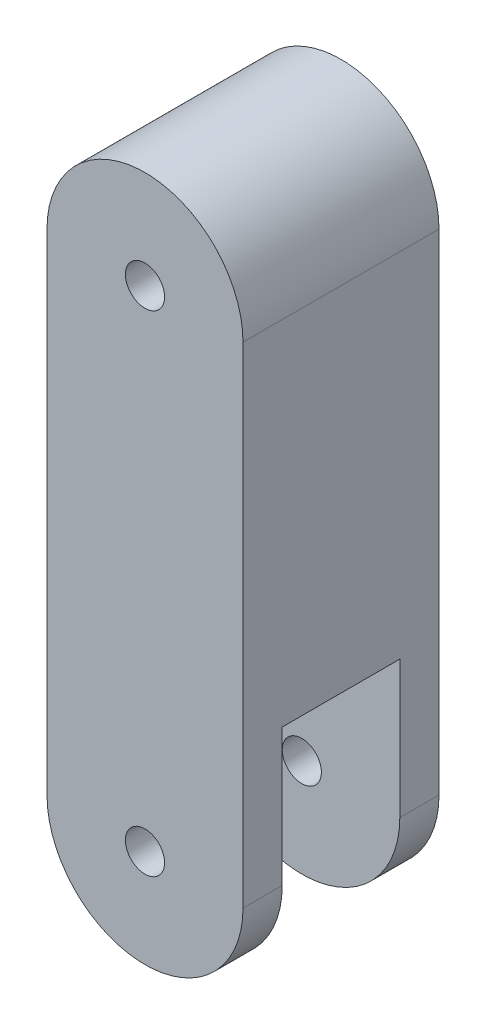
SolidWorks part; units mm, degrees
ref_plane "Alzado" through (0, 0, 0) normal (0, 0, 1) x (1, 0, 0)
ref_plane "Planta" through (0, 0, 0) normal (0, 1, 0) x (1, 0, 0)
ref_plane "Vista lateral" through (0, 0, 0) normal (1, 0, 0) x (0, 0, -1)
sketch "Croquis1" plane through (0, 0, 0) normal (0, 0, 1) x (1, 0, 0)
  line L0 (-2.5, 0) -> (-2.5, -12.5)
  line L3 (2.5, 0) -> (2.5, -12.5)
  line L7 (-2.5, -12.5) -> (-2.5, -10)
  line L8 (-2.5, -10) -> (2.5, -15) construction
  circle A0 centre (0, 0) radius 0.5
  arc A1 (2.5, 0) -> (-2.5, 0) centre (0, 0) ccw
  circle A2 centre (0, -12.5) radius 0.5
  arc A3 (-2.5, -12.5) -> (2.5, -12.5) centre (0, -12.5) ccw
  dimension "D1" = 1
  dimension "D2" = 5
  dimension "D8" = 1
  dimension "D6" = 15
extrude "Saliente-Extruir2" add sketch "Croquis1" along normal blind 5 contours L0 L8 A2 A3 L3 A1 A0 | L8 L0 A3 A2 region at (0.1253, -5.2662, 0) region at (-0.8749, -13.1169, 0)
sketch "Croquis3" plane through (2.5, 0, 0) normal (1, 0, 0) x (0, 0, -1)
  line L0 (-5, -12.5) -> (-5, -9)
  line L1 (-5, 0) -> (-5, -12.5) construction
  line L2 (-5, -9) -> (0, -9)
  line L3 (0, 0) -> (0, -12.5) construction
  line L4 (0, -9) -> (0, -15.6212)
  line L5 (0, -15.6212) -> (-1, -15.6212)
  line L6 (-1, -15.6212) -> (-1, -9)
  line L7 (-4, -9) -> (-4, -15.6212)
  line L8 (-4, -15.6212) -> (-5, -15.6212)
  line L9 (-5, -15.6212) -> (-5, -9)
  line L10 (-4, -15.6212) -> (-1, -15.6212)
  line M8 (-5, -12.5) -> (0, -12.5)
  dimension "D1" = 1
  dimension "D2" = 1
  dimension "D3" = 3.5
extrude "Cortar-Extruir2" cut sketch "Croquis3" against normal blind 5 contours L2 L7 L6 M8 | L7 L10 L6 M8 region at (2.5, -14.0606, 2.5) region at (2.5, -10.75, 2.5)
